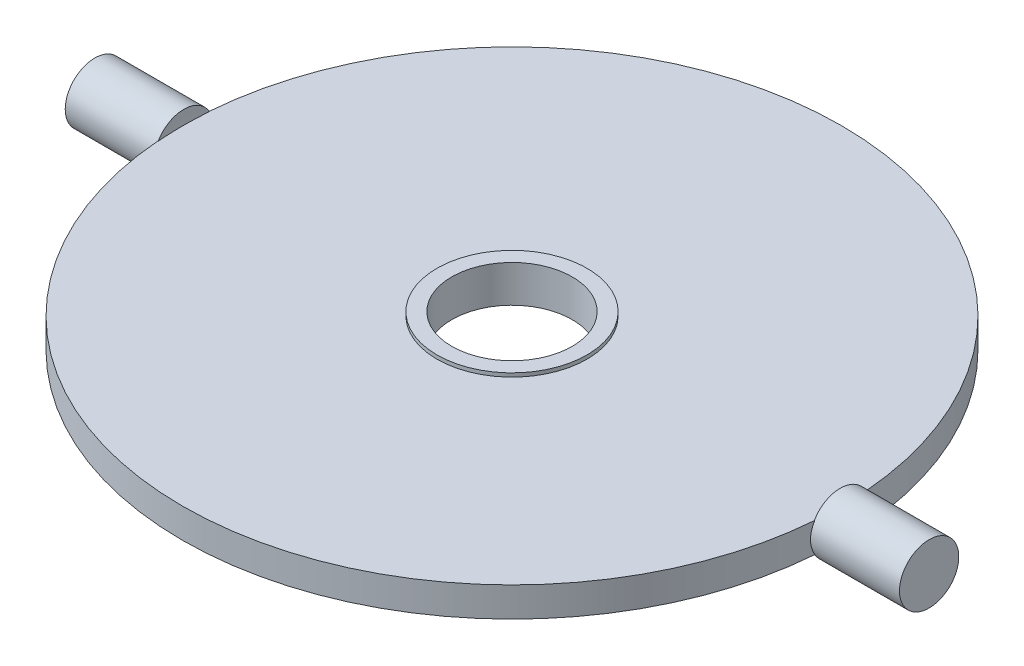
SolidWorks part; units mm, degrees
ref_plane "Front Plane" through (0, 0, 0) normal (0, 0, 1) x (1, 0, 0)
ref_plane "Top Plane" through (0, 0, 0) normal (0, 1, 0) x (1, 0, 0)
ref_plane "Right Plane" through (0, 0, 0) normal (1, 0, 0) x (0, 0, -1)
sketch "Sketch1" plane through (0, 0, 0) normal (0, 1, 0) x (1, 0, 0)
  line L0 (-76.4354, 0) -> (76.4354, 0) construction
  line L1 (-56.2697, 4) -> (-56.2697, -4)
  line L2 (0, 44.45) -> (0, -44.45) construction
  line L3 (-56.2697, 4) -> (-44.2697, 4)
  line L4 (-56.2697, -4) -> (-44.2697, -4)
  line L5 (56.2697, -4) -> (44.2697, -4)
  line L6 (56.2697, 4) -> (56.2697, -4)
  line L7 (56.2697, 4) -> (44.2697, 4)
  line L8 (-56.2697, 0) -> (-44.45, 0)
  line L9 (56.2697, 0) -> (44.45, 0)
  circle A0 centre (0, 0) radius 44.45
  circle A1 centre (0, 0) radius 8.125
  circle A2 centre (0, 0) radius 10.125
  point P6 (0, 0)
  point P9 (-56.2697, 0)
  dimension "D1" = 88.9
  dimension "D4" = 16.25
  dimension "D2" = 8
  dimension "D3" = 12
  dimension "D5" = 2
extrude "Boss-Extrude1" add sketch "Sketch1" along normal mid plane 4 contours A0 L1 region at (0, 0, -43.1928)
revolve "Revolve1" add sketch "Sketch1<6>" angle 360 about L0 region at (-50.3297, 0, 2.0051) region at (50.3297, 0, 2.0051)
sketch "Sketch1<6>" plane through (0, 0, 0) normal (0, 1, 0) x (1, 0, 0) same geometry as "Sketch1"
extrude "Boss-Extrude2" add sketch "Sketch1<7>" along normal mid plane 5 contours A2 A1 region at (-9.8386, 0, 0)
sketch "Sketch1<7>" plane through (0, 0, 0) normal (0, 1, 0) x (1, 0, 0) same geometry as "Sketch1"
sketch "Sketch2" plane through (0, 2, 0) normal (0, 1, 0) x (1, 0, 0)
  line L1 (-20.3, 8.751) -> (20.3, 8.751)
  line L2 (-20.3, 8.751) -> (-20.3, 29.925)
  line L3 (-20.3, 29.925) -> (20.3, 29.925)
  line L4 (20.3, 8.751) -> (20.3, 29.925)
  line L5 (-20.3, 8.751) -> (20.3, 29.925) construction
  line L6 (-20.3, 29.925) -> (20.3, 8.751) construction
  point P0 (0, 19.338)
sketch "Sketch3" plane through (0, -2, 0) normal (0, -1, 0) x (1, 0, 0)
  circle A0 centre (21.8622, -15.025) radius 2.2
  arc A1 (23.6725, -13.775) -> (23.6725, -16.275) centre (21.8622, -15.025) ccw construction
  circle A2 centre (21.8622, -25.025) radius 2.2
  circle A3 centre (-27.9171, -15.025) radius 2.2
  arc A4 (-29.7275, -16.275) -> (-29.7275, -13.775) centre (-27.9171, -15.025) ccw construction
  arc A5 (23.6725, -23.775) -> (23.6725, -26.275) centre (21.8622, -25.025) ccw construction
  circle A6 centre (-27.9171, -25.025) radius 2.2
  arc A7 (-29.7275, -26.275) -> (-29.7275, -23.775) centre (-27.9171, -25.025) ccw construction
